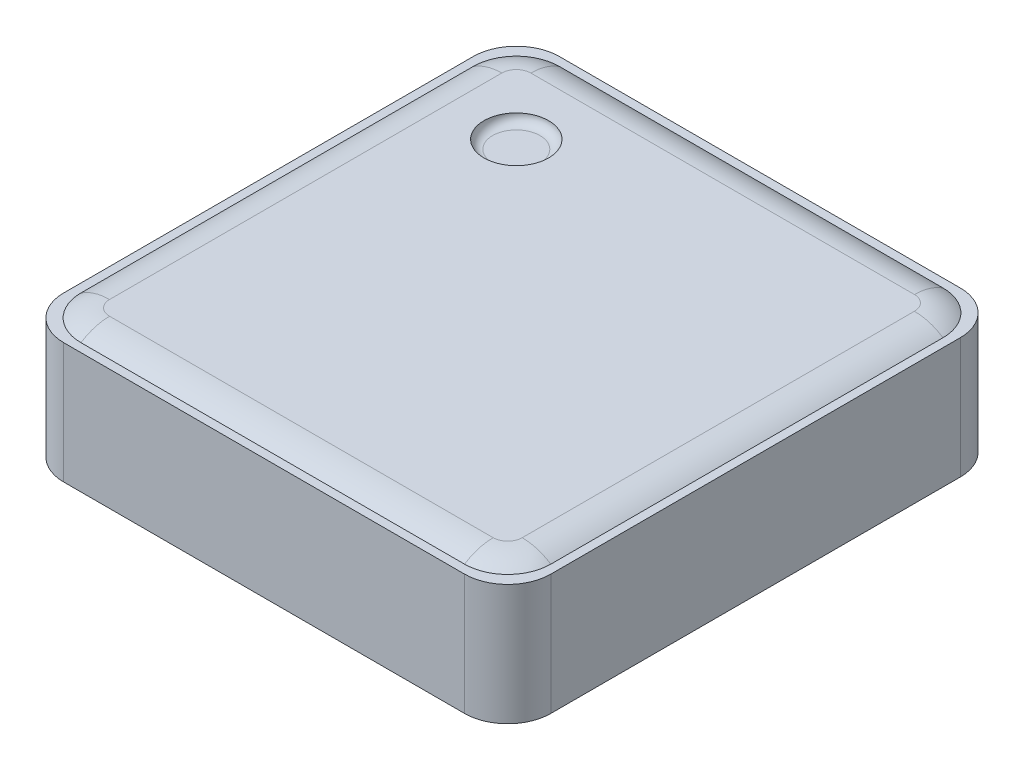
SolidWorks part; units mm, degrees
material "PVC Rígido"
ref_plane "Plano frontal" through (0, 0, 0) normal (0, 0, 1) x (1, 0, 0)
ref_plane "Plano superior" through (0, 0, 0) normal (0, 1, 0) x (1, 0, 0)
ref_plane "Plano direito" through (0, 0, 0) normal (1, 0, 0) x (0, 0, -1)
sketch "Esboço1" plane through (0, 0, 0) normal (0, 1, 0) x (1, 0, 0)
  line L1 (56.5, 57.5) -> (-56.5, 57.5)
  line L2 (56.5, 57.5) -> (56.5, -57.5)
  line L3 (56.5, -57.5) -> (-56.5, -57.5)
  line L4 (-56.5, 57.5) -> (-56.5, -57.5)
  line L5 (56.5, 57.5) -> (-56.5, -57.5) construction
  line L6 (56.5, -57.5) -> (-56.5, 57.5) construction
  point P0 (0, 0)
  dimension "D1" = 115
  dimension "D2" = 113
extrude "Ressalto-extrusão1" add sketch "Esboço1" along normal blind 30
sketch "Esboço2" plane through (0, 30, 0) normal (0, 1, 0) x (1, 0, 0)
  line L1 (-54.5, 55.5) -> (54.5, 55.5)
  line L2 (-54.5, 55.5) -> (-54.5, -55.5)
  line L3 (-54.5, -55.5) -> (54.5, -55.5)
  line L4 (54.5, 55.5) -> (54.5, -55.5)
  line L5 (-54.5, 55.5) -> (54.5, -55.5) construction
  line L6 (-54.5, -55.5) -> (54.5, 55.5) construction
  line L7 (-56.5, 57.5) -> (56.5, 57.5)
  line L8 (-56.5, 57.5) -> (-56.5, -57.5)
  line L9 (-56.5, -57.5) -> (56.5, -57.5)
  line L10 (56.5, 57.5) -> (56.5, -57.5)
  line L11 (-56.5, 57.5) -> (56.5, -57.5) construction
  line L12 (-56.5, -57.5) -> (56.5, 57.5) construction
  point P0 (0, 0)
  point P6 (0, 0)
  dimension "D1" = 2
  dimension "D2" = 2
extrude "Corte-extrusão1" cut sketch "Esboço2" against normal blind 2
fillet "Filete1" radius 10 8 edges at (54.5, 29, -55.5) (54.5, 29, 55.5) (-54.5, 29, 55.5) (-54.5, 29, -55.5) (56.5, 14, 57.5) (56.5, 14, -57.5) (-56.5, 14, 57.5) (-56.5, 14, -57.5)
fillet "Filete2" radius 12 8 edges at (51.5711, 30, 52.5711) (0, 30, 55.5) (-51.5711, 30, 52.5711) (-54.5, 30, 0) (-51.5711, 30, -52.5711) (0, 30, -55.5) (51.5711, 30, -52.5711) (54.5, 30, 0)
sketch "Esboço3" plane through (0, 30, 0) normal (0, 1, 0) x (1, 0, 0)
  line L1 (-47.8668, 45.5) -> (-47.8668, -45.5) construction
  line L2 (44.5, 48.8668) -> (-44.5, 48.8668) construction
  circle A0 centre (-32.8668, 33.8668) radius 7.5
  dimension "D1" = 15
  dimension "D3" = 15
  dimension "D2" = 15
extrude "Corte-extrusão2" cut sketch "Esboço3" against normal blind 2
fillet "Filete3" radius 2 1 edges at (-32.8668, 28, -26.3668) type face fillet first side face at (-32.8668, 28, -26.3668) second side face at (-32.8668, 28, -26.3668)
